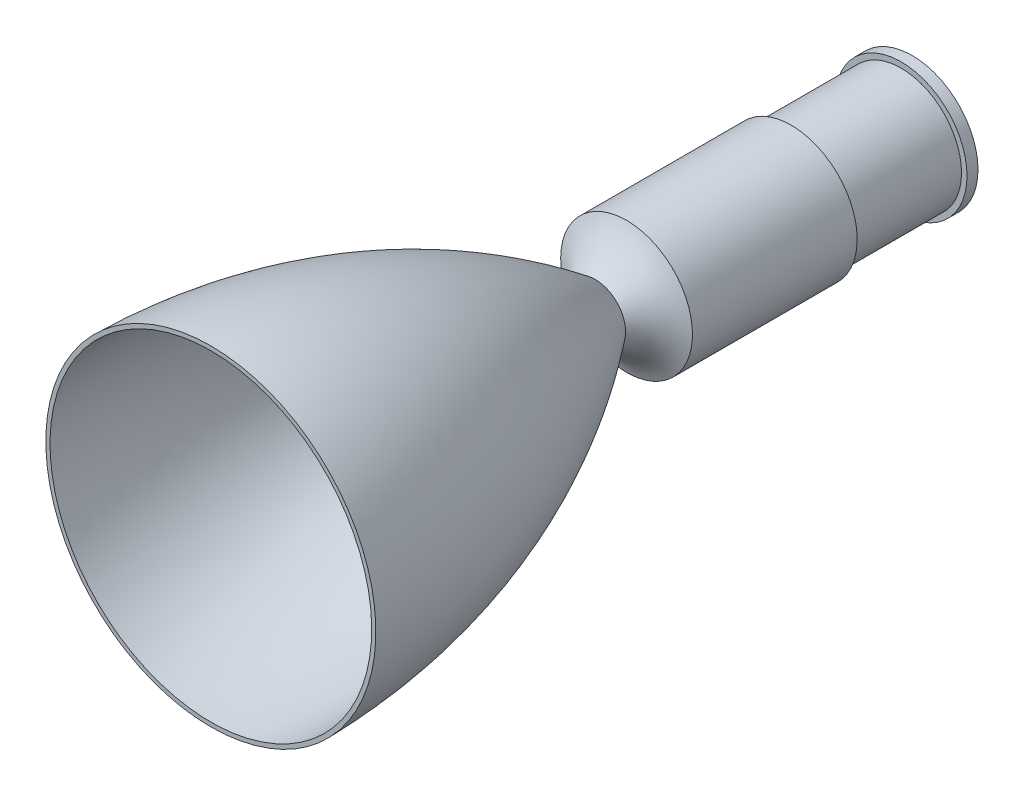
SolidWorks part; units mm, degrees
material "201 Annealed Stainless Steel (SS)"
ref_plane "Front Plane" through (0, 0, 0) normal (0, 0, 1) x (1, 0, 0)
ref_plane "Top Plane" through (0, 0, 0) normal (0, 1, 0) x (1, 0, 0)
ref_plane "Right Plane" through (0, 0, 0) normal (1, 0, 0) x (0, 0, -1)
sketch "Sketch1" plane through (0, 0, 0) normal (0, 0, 1) x (1, 0, 0)
  circle A0 centre (0, 0) radius 17.78
extrude "Boss-Extrude1" add sketch "Sketch1" along normal blind 5.08
sketch "Sketch2" plane through (0, 0, 5.08) normal (0, 0, 1) x (1, 0, 0)
  circle A0 centre (0, 0) radius 30.48
extrude "Boss-Extrude2" add sketch "Sketch2" along normal blind 5.08
sketch "Sketch3" plane through (0, 0, 10.16) normal (0, 0, 1) x (1, 0, 0)
  circle A0 centre (0, 0) radius 27.94
extrude "Boss-Extrude3" add sketch "Sketch3" along normal blind 50.8
sketch "Sketch4" plane through (0, 0, 60.96) normal (0, 0, 1) x (1, 0, 0)
  circle A0 centre (0, 0) radius 30.48 construction
  circle A1 centre (0, 0) radius 30.48
extrude "Boss-Extrude4" add sketch "Sketch4" along normal blind 76.2
sketch "Sketch5" plane through (0, 0, 0) normal (1, 0, 0) x (0, 0, -1)
  line L0 (-137.16, 30.48) -> (-137.16, 26.5602)
  line L1 (-137.16, 0) -> (-329.438, 0) construction
  line L2 (-137.16, 30.48) -> (-137.16, -30.48) construction
  line L4 (-329.438, 76.327) -> (-329.438, 74.399)
  spline S0 degree 2 poles (-151.5992, 14) (-230.0584, 74.3121) (-329.438, 76.327) knots 0 0 0 1 1 1
  spline S1 degree 2 poles (-151.5992, 14) (-141.4995, 19.827) (-137.16, 30.48) knots 0 0 0 1 1 1
  spline S2 degree 2 poles (-151.5992, 12.3906) (-141.9865, 17.1646) (-137.16, 26.5602) knots 0 0 0 1 1 1
  spline S3 degree 2 poles (-151.5992, 12.3906) (-229.8988, 73.1374) (-329.438, 74.399) knots 0 0 0 1 1 1
revolve "Revolve1" add sketch "Sketch5" angle 360 about L1
